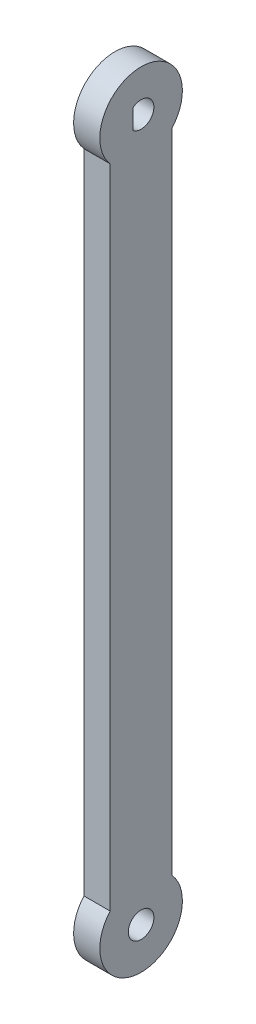
SolidWorks part; units mm, degrees
ref_plane "Front Plane" through (0, 0, 0) normal (0, 0, 1) x (1, 0, 0)
ref_plane "Top Plane" through (0, 0, 0) normal (0, 1, 0) x (1, 0, 0)
ref_plane "Right Plane" through (0, 0, 0) normal (1, 0, 0) x (0, 0, -1)
sketch "Sketch1" plane through (0, 0, 0) normal (1, 0, 0) x (0, 0, -1)
  line L0 (0, 0) -> (-3.75, -3.3072) construction
  line L2 (3.75, -3.3072) -> (3.75, -81.6928)
  line L3 (3.75, -81.6928) -> (-3.75, -81.6928) construction
  line L4 (-3.75, -3.3072) -> (-3.75, -81.6928)
  line L5 (3.75, -3.3072) -> (-3.75, -3.3072) construction
  line L6 (0, 0) -> (3.75, -3.3072) construction
  line L7 (-1, 1.1843) -> (-1, -1.1843)
  arc A0 (-1, -1.1843) -> (-1, 1.1843) centre (0, 0) ccw
  arc A1 (3.75, -3.3072) -> (-3.75, -3.3072) centre (0, 0) ccw
  arc A2 (-3.75, -81.6928) -> (3.75, -81.6928) centre (0, -85) ccw
  circle A3 centre (0, -85) radius 1.55
  point P11 (-1, -1.9728)
  point P12 (-1, 1.1843)
  dimension "D1" = 3.1
  dimension "D2" = 10
  dimension "D4" = 10
  dimension "D6" = 3.1
  dimension "D3" = 7.5
  dimension "D5" = 85
  dimension "D7" = 1
extrude "Boss-Extrude3" add sketch "Sketch1" along normal blind 3.175
